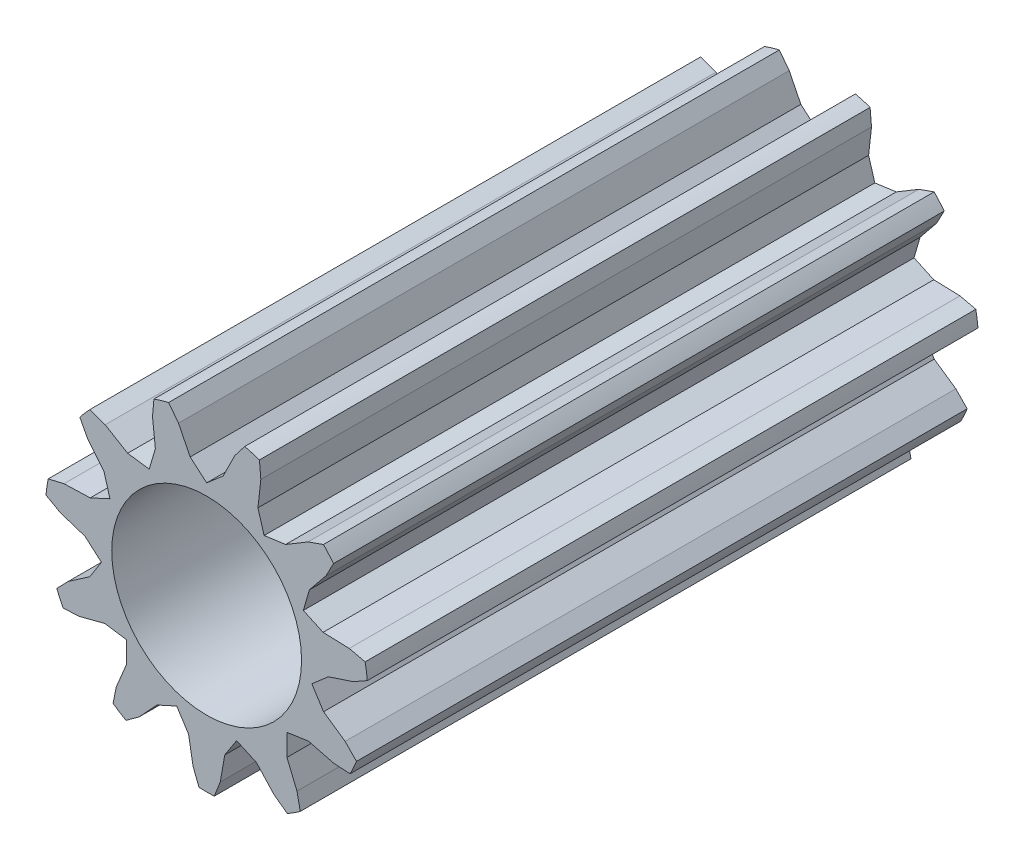
SolidWorks part; units mm, degrees
ref_plane "Front Plane" through (0, 0, 0) normal (0, 0, 1) x (1, 0, 0)
ref_plane "Top Plane" through (0, 0, 0) normal (0, 1, 0) x (1, 0, 0)
ref_plane "Right Plane" through (0, 0, 0) normal (1, 0, 0) x (0, 0, -1)
sketch "Sketch1" plane through (0, 0, 0) normal (0, 0, 1) x (1, 0, 0)
  line L1 (4.0659, -4.0659) -> (-4.0659, -4.0659) construction
  line L2 (4.0659, -4.0659) -> (4.0659, 4.0659) construction
  line L3 (4.0659, 4.0659) -> (-4.0659, 4.0659) construction
  line L4 (-4.0659, -4.0659) -> (-4.0659, 4.0659) construction
  line L5 (4.0659, -4.0659) -> (-4.0659, 4.0659) construction
  line L6 (4.0659, 4.0659) -> (-4.0659, -4.0659) construction
  circle A0 centre (0, 0) radius 9.7778
  circle A1 centre (0, 0) radius 5.75 construction
  dimension "D1" = 19.5556
  dimension "D2" = 11.5
extrude "Boss-Extrude1" add sketch "Sketch1" along normal blind 37
sketch "Sketch2" plane through (0, 0, 0) normal (0, 0, 1) x (1, 0, 0)
  line L0 (0, 0) -> (0, 10.088) construction
  line L1 (0, 6.4402) -> (-0.9985, 7.2997)
  line L8 (-1.7043, 10.285) -> (0, 10.9993)
  line L11 (-0.9985, 7.2997) -> (-1.7043, 8.7207)
  line L12 (-1.7043, 8.7207) -> (-2.3066, 9.5018)
  line L13 (-2.3066, 9.5018) -> (-1.7043, 10.285)
  line L14 (2.3066, 9.5018) -> (1.7043, 10.285)
  line L15 (1.7043, 8.7207) -> (2.3066, 9.5018)
  line L16 (0.9985, 7.2997) -> (1.7043, 8.7207)
  line L17 (1.7043, 10.285) -> (0, 10.9993)
  line L18 (0, 6.4402) -> (0.9985, 7.2997)
  circle A14 centre (0, 0) radius 9.7778 construction
  point P16 (0, 9.7778)
  dimension "D5" = 0.6023
  dimension "D6" = 0.7811
  dimension "D1" = 0.9985
  dimension "D2" = 0.8594
  dimension "D3" = 0.7058
  dimension "D4" = 1.4211
  dimension "D7" = 0.7832
  dimension "D8" = 0.6023
  dimension "D9" = 0.7142
  dimension "D10" = 1.7043
extrude "Cut-Extrude1" cut sketch "Sketch2" along normal through all
sketch "Sketch3" plane through (0, 0, 0) normal (0, 0, 1) x (1, 0, 0)
  circle A0 centre (0, 0) radius 7.5
  dimension "D1" = 15
sketch "Sketch4" plane through (0, 0, 37) normal (0, 0, 1) x (1, 0, 0)
  circle A0 centre (0, 0) radius 5.75
  dimension "D1" = 11.5
extrude "Cut-Extrude2" cut sketch "Sketch4" against normal through all both and the other way through all
pattern_circular "CirPattern1" count 11 over 360 about axis through (0, 0, 37) along (0, 0, -1) of "Cut-Extrude1" reverse direction yes
sketch "Sketch5" plane through (0, 0, 0) normal (0, 0, 1) x (1, 0, 0)
  line L0 (0, 0) -> (0, 16.5734) construction
  arc A0 (0, 2.7703) -> (-2.7395, 5.5802) centre (3.9333, 9.3453) cw
  arc A1 (-2.7395, 5.5802) -> (0, 7.0858) centre (3.4783, -2.4876) cw
  arc A2 (2.7395, 5.5802) -> (0, 7.0858) centre (-3.4783, -2.4876) ccw
  arc A3 (0, 2.7703) -> (2.7395, 5.5802) centre (-3.9333, 9.3453) ccw
equation "\"circle\"=19.5556"
equation "\"D1@Sketch1\"=\"circle\""
equation "\"separator_width\"=45"
equation "\"big-gear-thiccness\"=2"
equation "\"D1@Boss-Extrude1\"=\"separator_width\" - \"big-gear-thiccness\"-10/2+2-3"
